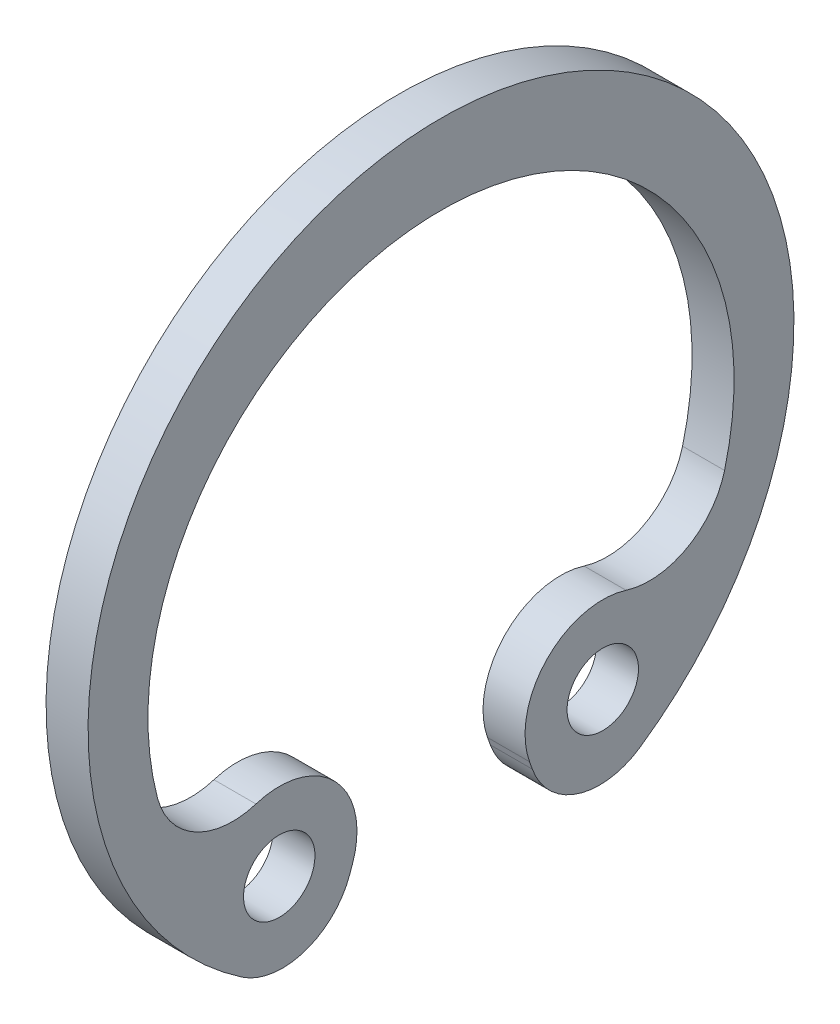
SolidWorks part; units mm, degrees
ref_plane "Front Plane" through (0, 0, 0) normal (0, 0, 1) x (1, 0, 0)
ref_plane "Top Plane" through (0, 0, 0) normal (0, 1, 0) x (1, 0, 0)
ref_plane "Right Plane" through (0, 0, 0) normal (1, 0, 0) x (0, 0, -1)
ref_plane "Plane1" through (0, 0, 0) normal (1, 0, 0) x (0, 0, -1)
sketch "Sketch1" plane through (0, 0, 0) normal (1, 0, 0) x (0, 0, -1)
  line L0 (-2.1733, -6.1055) -> (-2.1071, -5.9195)
  line L1 (2.1071, -5.9195) -> (2.1733, -6.1055)
  arc A0 (4.7327, -6.9398) -> (-4.7327, -6.9398) centre (0, 0) ccw
  arc A1 (-4.7327, -6.9398) -> (-2.1733, -6.1055) centre (-3.7749, -5.5354) ccw
  arc A2 (-2.1071, -5.9195) -> (-4.4045, -3.5341) centre (-3.85, -5.2991) ccw
  arc A3 (-4.4045, -3.5341) -> (-6.749, -2.2363) centre (-4.9589, -1.7691) cw
  arc A4 (-6.749, -2.2363) -> (6.749, -2.2363) centre (0, -0.475) cw
  arc A5 (6.749, -2.2363) -> (4.4045, -3.5341) centre (4.9589, -1.7691) cw
  arc A6 (4.4045, -3.5341) -> (2.1071, -5.9195) centre (3.85, -5.2991) ccw
  arc A7 (2.1733, -6.1055) -> (4.7327, -6.9398) centre (3.7749, -5.5354) ccw
  circle A8 centre (3.85, -5.2991) radius 0.85
  circle A9 centre (-3.85, -5.2991) radius 0.85
extrude "Boss-Extrude1" add sketch "Sketch1" against normal blind 0.5 and the other way blind 0.5
